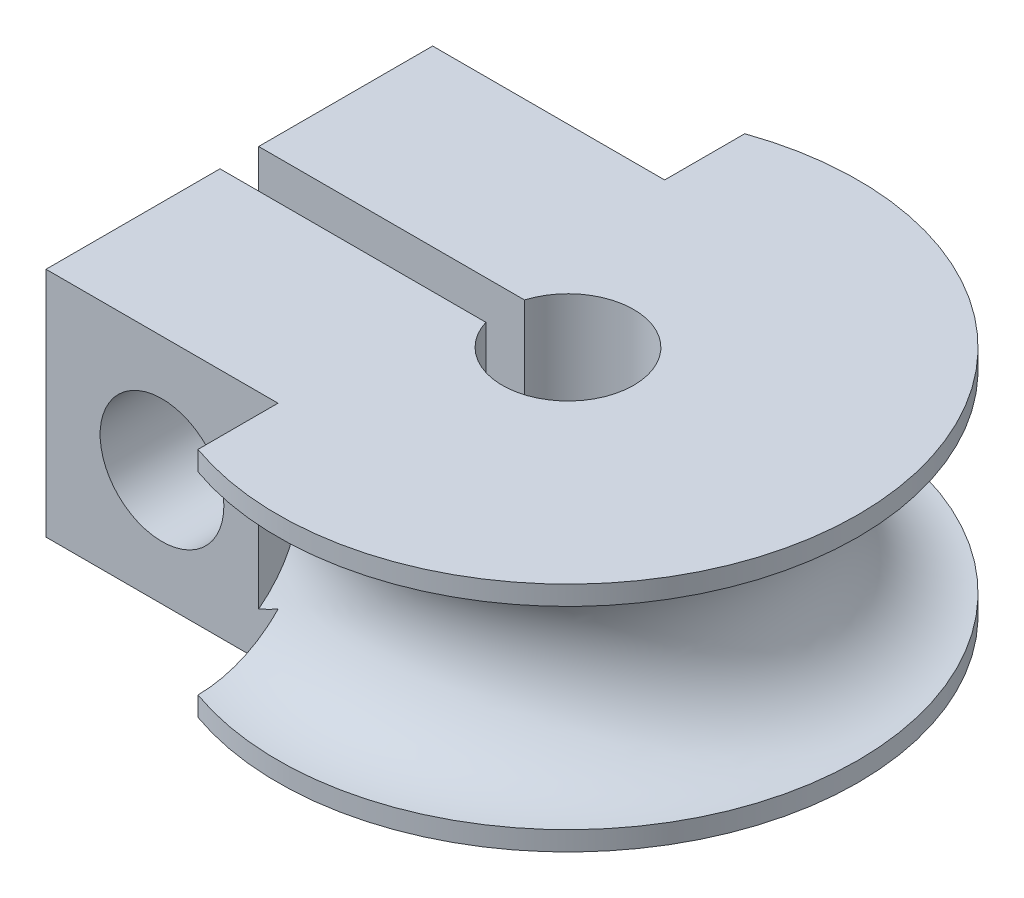
SolidWorks part; units mm, degrees
material "PET"
ref_plane "Front Plane" through (0, 0, 0) normal (0, 0, 1) x (1, 0, 0)
ref_plane "Top Plane" through (0, 0, 0) normal (0, 1, 0) x (1, 0, 0)
ref_plane "Right Plane" through (0, 0, 0) normal (1, 0, 0) x (0, 0, -1)
sketch "Sketch1" plane through (0, 0, 0) normal (0, 0, 1) x (1, 0, 0)
  line L0 (0, 0) -> (0, 6.5) construction
  line L1 (3, 0) -> (4, 0)
  line L2 (4, 0) -> (4, 0.5)
  line L3 (4, 0.5) -> (7.5, 0.5)
  line L4 (7.5, 0.5) -> (7.5, 1)
  line L5 (7.5, 6) -> (7.5, 6.5)
  line L6 (7.5, 6.5) -> (1.7, 6.5)
  line L8 (1.7, 6.5) -> (1.7, 4)
  line L9 (1.7, 4) -> (3, 4)
  line L10 (3, 4) -> (3, 0)
  arc A0 (7.5, 1) -> (7.5, 6) centre (7.5, 3.5) cw
  point P10 (5, 3.5)
  point P15 (0, 0)
  dimension "D6" = 2.5
  dimension "D1" = 3.4
  dimension "D2" = 6
  dimension "D3" = 4
  dimension "D4" = 0.5
  dimension "D5" = 0.5
  dimension "D7" = 5
  dimension "D8" = 8
revolve "body" add sketch "Sketch1" angle 360 about L0
sketch "Sketch2" plane through (0, 0, 0) normal (0, 0, 1) x (1, 0, 0)
  line L1 (7.5, 6.5) -> (-7.5, 6.5) construction
  line L2 (-3, 6.5) -> (-8.5, 6.5)
  line L3 (-8.5, 6.5) -> (-8.5, 0.5)
  line L9 (-3, 6.5) -> (-3, 0.5)
  line L10 (-4, 0.5) -> (4, 0.5) construction
  line L11 (-3, 0.5) -> (-8.5, 0.5)
  point P0 (0, 0)
  dimension "D1" = 3
  dimension "D2" = 5.5
extrude "clamp_extrusion" add sketch "Sketch2" along normal blind 5 and the other way blind 5
sketch "Sketch3" plane through (0, 6.5, 0) normal (0, 1, 0) x (1, 0, 0)
  line L0 (-8.5, 5) -> (-2.5, 5)
  line L1 (-2.5, 5) -> (-2.5, 7.0711)
  line L2 (-2.5, 7.0711) -> (-8.5, 7.0711)
  line L3 (-8.5, 7.0711) -> (-8.5, 5)
  line L4 (-8.5, -5) -> (-2.5, -5)
  line L5 (-2.5, -5) -> (-2.5, -7.0711)
  line L6 (-2.5, -7.0711) -> (-8.5, -7.0711)
  line L7 (-8.5, -7.0711) -> (-8.5, -5)
  line L8 (-8.5, 5) -> (-8.5, -5) construction
  line L9 (-8.5, -0.5) -> (0, -0.5)
  line L10 (-8.5, -0.5) -> (-8.5, 0.5)
  line L11 (-8.5, 0.5) -> (0, 0.5)
  line L12 (0, -0.5) -> (0, 0.5)
  arc A0 (-5.5902, -5) -> (-5.5902, 5) centre (0, 0) ccw construction
  point P19 (0, 0)
  dimension "D1" = 1
  dimension "D2" = 6
extrude "clamp_cutout" cut sketch "Sketch3" against normal through all
sketch "clamp_hole_pos" plane through (0, 0, 5) normal (0, 0, 1) x (1, 0, 0)
  line L0 (-8.5, 6.5) -> (-8.5, 0.5) construction
  point P0 (-5.5, 3.5)
  point P1 (0, 0)
  point P3 (0, 0)
  point P6 (-8.5, 3.5)
  dimension "D1" = 5.5
hole_wizard "clamp_hole" positions "clamp_hole_pos" profile "Sketch5" hole size "M3" standard "DIN" end condition through all
sketch "Sketch5" plane through (-5.5, 3.5, 5) normal (1, 0, 0) x (0, -1, 0)
  line L0 (0, 0) -> (0, 12.5)
  line L1 (0, 12.5) -> (1.6, 12.5)
  line L2 (1.6, 12.5) -> (1.6, 0)
  line L5 (1.6, 0) -> (0, 0)
  line L11 (0, -6.35) -> (0, 107.95) construction
  dimension "Thru Hole Dia." = 3.2
  dimension "Thru Hole Depth" = 12.5
